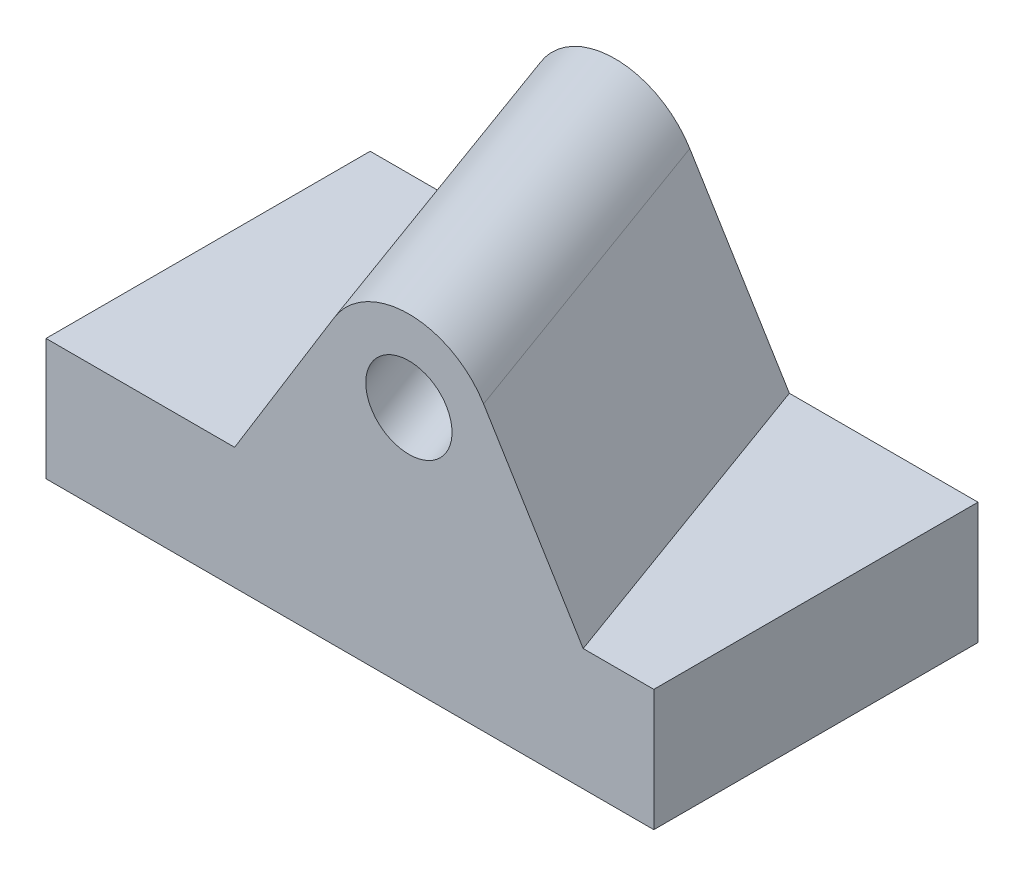
SolidWorks part; units mm, degrees
ref_plane "Front Plane" through (0, 0, 0) normal (0, 0, 1) x (1, 0, 0)
ref_plane "Top Plane" through (0, 0, 0) normal (0, 1, 0) x (1, 0, 0)
ref_plane "Right Plane" through (0, 0, 0) normal (1, 0, 0) x (0, 0, -1)
sketch "Sketch1" plane through (0, 0, 0) normal (0, 0, 1) x (1, 0, 0)
  line L0 (-75, 0) -> (75, 0)
  line L1 (-75, 0) -> (-75, 30)
  line L3 (75, 0) -> (75, 30)
  line L4 (75, 30) -> (-75, 30)
  line L8 (0, 0) -> (0, 72.4489) construction
  dimension "D1" = 150
  dimension "D2" = 30
extrude "Boss-Extrude1" add sketch "Sketch1" along normal blind 80
ref_point "Point2"
ref_axis "Axis2" through (0, 30, 40) along (0, 1, 0)
ref_plane "Plane4" through (12.8558, 0, 35.3209) normal (0.342, 0, 0.9397) x (0, 1, 0)
sketch "Sketch3" plane through (12.8558, 0, 35.3209) normal (0.342, 0, 0.9397) x (0, 1, 0)
  line L0 (30, 92.4096) -> (30, -56.7961) construction
  line L1 (30, -43.1153) -> (30, 97.8386) construction
  line L2 (30, -43.1153) -> (30, -70.4769) construction
  line L4 (30, -26.7337) -> (70, -3.6397)
  line L5 (30, 13.6808) -> (86.1, 13.6808) construction
  line L6 (70, 31.0013) -> (30, 54.0953)
  line L7 (30, 54.0953) -> (30, -26.7337)
  line L8 (30, 13.6808) -> (80, 13.6808) construction
  arc A0 (70, -3.6397) -> (70, 31.0013) centre (60, 13.6808) ccw
  circle A1 centre (60, 13.6808) radius 10
  point P13 (80, 13.6808)
  dimension "D1" = 20
  dimension "D2" = 20
  dimension "D4" = 50
  dimension "D3" = 60
extrude "Boss-Extrude4" add sketch "Sketch3" along normal up to surface and the other way up to surface up to face at (0, 15, 80) other way up to face at (0, 15, 0)
